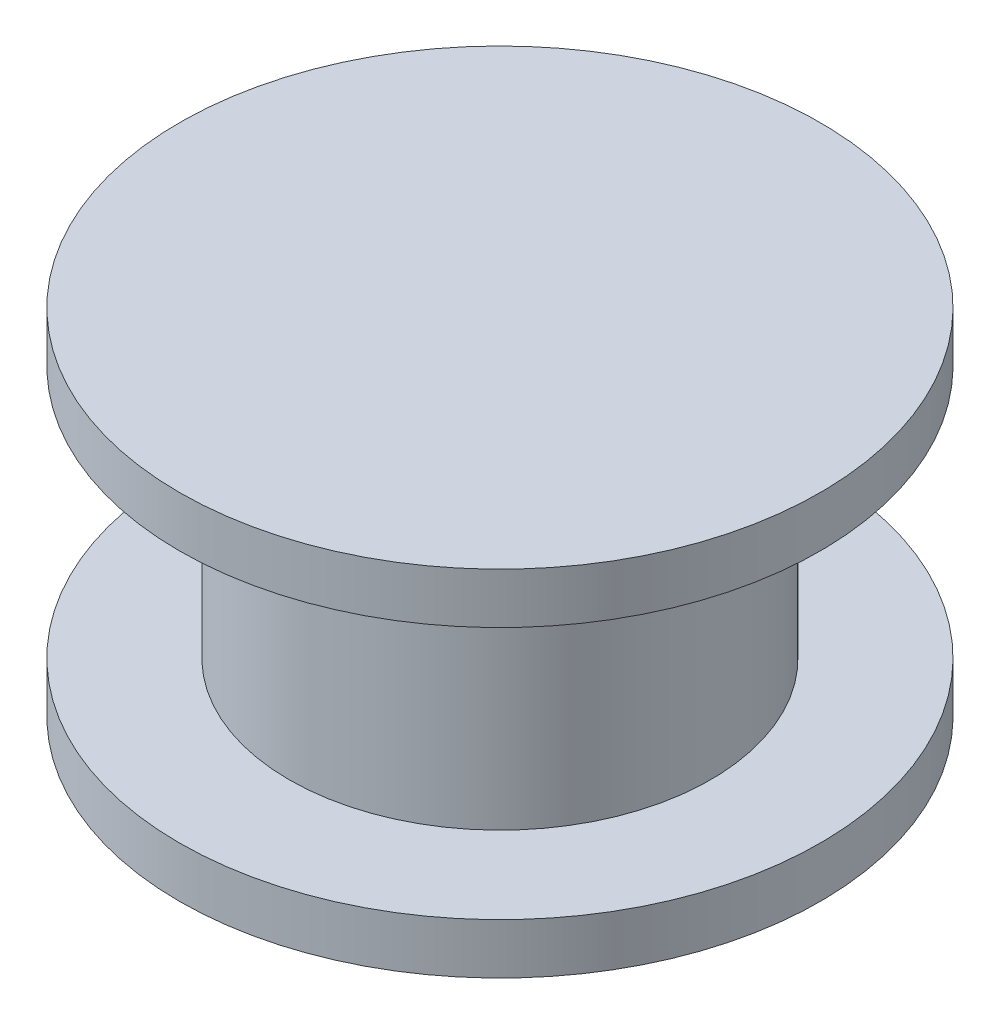
SolidWorks part; units mm, degrees
ref_plane "Front Plane" through (0, 0, 0) normal (0, 0, 1) x (1, 0, 0)
ref_plane "Top Plane" through (0, 0, 0) normal (0, 1, 0) x (1, 0, 0)
ref_plane "Right Plane" through (0, 0, 0) normal (1, 0, 0) x (0, 0, -1)
sketch "Sketch1" plane through (0, 0, 0) normal (0, 1, 0) x (1, 0, 0)
  circle A0 centre (0, 0) radius 9.5
  dimension "D1" = 19
extrude "Boss-Extrude1" add sketch "Sketch1" along normal blind 1.5
sketch "Sketch2" plane through (0, 1.5, 0) normal (0, 1, 0) x (1, 0, 0)
  circle A0 centre (0, 0) radius 6.25
  dimension "D1" = 12.5
extrude "Boss-Extrude2" add sketch "Sketch2" along normal blind 7.5
sketch "Sketch4" plane through (0, 9, 0) normal (0, 1, 0) x (1, 0, 0)
  circle A0 centre (0, 0) radius 9.5
  point P3 (-2.2636, 0.3124)
  point P4 (0, 0)
  point P5 (0, 0)
  dimension "D1" = 19
extrude "Boss-Extrude4" add sketch "Sketch4" along normal blind 1.5 contours A0
